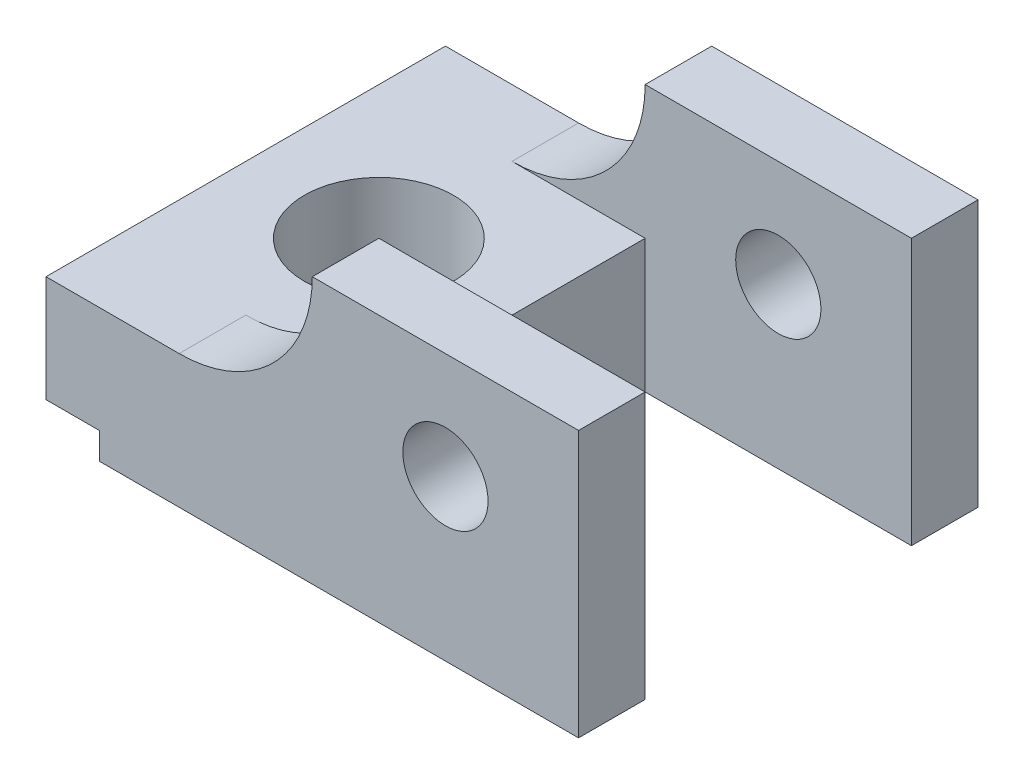
SolidWorks part; units mm, degrees
ref_plane "Alzado" through (0, 0, 0) normal (0, 0, 1) x (1, 0, 0)
ref_plane "Planta" through (0, 0, 0) normal (0, 1, 0) x (1, 0, 0)
ref_plane "Vista lateral" through (0, 0, 0) normal (1, 0, 0) x (0, 0, -1)
sketch "Croquis1" plane through (0, 0, 0) normal (0, 0, 1) x (1, 0, 0)
  line L0 (10, 4) -> (20, 4) construction
  line L1 (0, 0) -> (10, 0)
  line L2 (0, 0) -> (0, 4)
  line L3 (0, 4) -> (10, 4)
  line L4 (20, 0) -> (20, 4)
  line L6 (10, 0) -> (10, -1)
  line L7 (10, -1) -> (20, -1)
  line L8 (20, 0) -> (20, -1)
  line L10 (20, 4) -> (20, 9)
  line L11 (20, 9) -> (10, 9)
  line L12 (10, 4) -> (10, 9)
  line L13 (10, 0) -> (20, 0) construction
  line L14 (10, 9) -> (20, -1) construction
  line L15 (15, 5) -> (15, 9) construction
  circle A0 centre (15, 5) radius 1.6
  dimension "D5" = 3.2
  dimension "D1" = 4
  dimension "D2" = 10
  dimension "D3" = 1
  dimension "D4" = 10
  dimension "D6" = 10
  dimension "D7" = 4
extrude "Saliente-Extruir1" add sketch "Croquis1" along normal blind 15
sketch "Croquis2" plane through (0, 9, 0) normal (0, 1, 0) x (1, 0, 0)
  line L0 (20, -15) -> (20, 0) construction
  line L1 (20, -12.5) -> (10, -12.5)
  line L2 (20, -12.5) -> (20, -2.5)
  line L3 (20, -2.5) -> (10, -2.5)
  line L4 (10, -12.5) -> (10, -2.5)
  line L5 (10, -15) -> (10, 0) construction
  line L6 (0, -7.5) -> (10, -7.5) construction
  line L7 (0, -15) -> (0, 0) construction
  dimension "D1" = 10
extrude "Cortar-Extruir1" cut sketch "Croquis2" against normal blind 20
fillet "Redondeo1" radius 5 2 edges at (10, 4, 1.25) (10, 4, 13.75)
sketch "Croquis3" plane through (0, 4, 0) normal (0, 1, 0) x (1, 0, 0)
  line L0 (0, -7.5) -> (10, -7.5) construction
  line L1 (0, -15) -> (0, 0) construction
  line L2 (10, -12.5) -> (10, -2.5) construction
  circle A2 centre (5, -7.5) radius 1.9745
extrude "Cortar-Extruir2" cut sketch "Croquis3" against normal blind 11.2
sketch "Croquis4" plane through (0, 4, 0) normal (0, 1, 0) x (1, 0, 0)
  circle A0 centre (5, -7.5) radius 2.8
  dimension "D1" = 5.6
extrude "Cortar-Extruir3" cut sketch "Croquis4" against normal blind 3
sketch "Croquis6" plane through (0, 0, 0) normal (0, -1, 0) x (1, 0, 0)
  line L0 (0, 15) -> (10, 15) construction
  line L1 (10, 0) -> (2, 0)
  line L2 (10, 0) -> (10, 15)
  line L3 (10, 15) -> (2, 15)
  line L4 (2, 0) -> (2, 15)
  circle A0 centre (5, 7.5) radius 1.9745 construction
  circle A1 centre (5, 7.5) radius 1.9745
  dimension "D1" = 3
extrude "Saliente-Extruir2" add sketch "Croquis6" along normal blind 1
